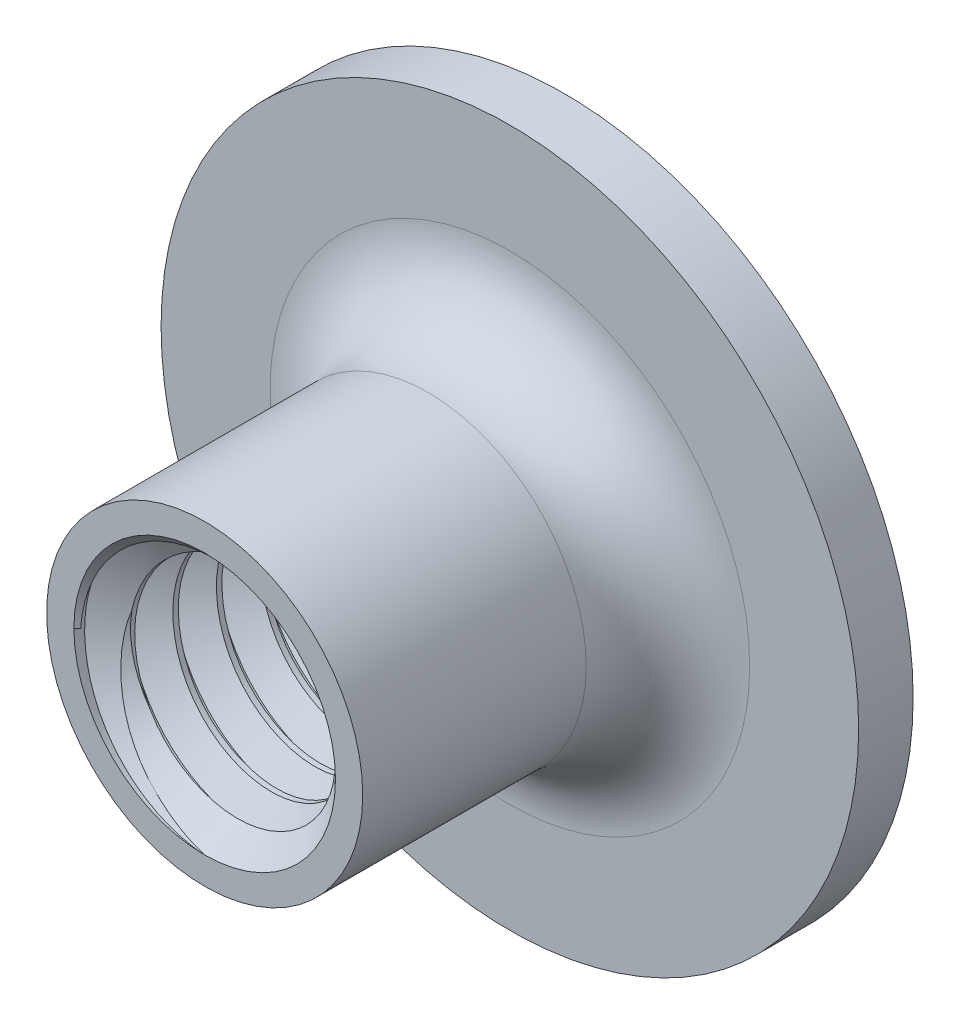
SolidWorks part; units mm, degrees
ref_plane "Front Plane" through (0, 0, 0) normal (0, 0, 1) x (1, 0, 0)
ref_plane "Top Plane" through (0, 0, 0) normal (0, 1, 0) x (1, 0, 0)
ref_plane "Right Plane" through (0, 0, 0) normal (1, 0, 0) x (0, 0, -1)
sketch "Sketch1" plane through (0, 0, 0) normal (0, 0, 1) x (1, 0, 0)
  circle A0 centre (0, 0) radius 12.7
  circle A1 centre (0, 0) radius 4.7625
  dimension "D1" = 9.525
extrude "Extrude1" add sketch "Sketch1" along normal blind 1.9844
sketch "Sketch2" plane through (0, 0, 1.9844) normal (0, 0, 1) x (1, 0, 0)
  circle A0 centre (0, 0) radius 5.7547
  circle A1 centre (0, 0) radius 4.7625
extrude "Extrude2" add sketch "Sketch2" along normal blind 11.1125
sketch "Sketch3" plane through (0, 0, 0) normal (0, 0, -1) x (-1, 0, 0)
  circle A0 centre (0, 0) radius 4.7625 construction
  circle A1 centre (0, 0) radius 4.7625
curve "Helix/Spiral1" pitch 1.5875 height 14.2875 turns 9 parameters "pitch"=1.5875
sketch "Sketch4" plane through (0, 0, 0) normal (0, 1, 0) x (1, 0, 0)
  line L0 (-4.7625, 1.3891) -> (-4.7625, 0)
  line L1 (-4.7625, 0) -> (-3.7314, 0.5953)
  line L2 (-3.7314, 0.5953) -> (-3.7314, 0.7938)
  line L3 (-3.7314, 0.7938) -> (-4.7625, 1.3891)
  line L4 (-3.7314, 0.6945) -> (-4.7625, 0.6945) construction
  line L5 (-4.2469, 0.2977) -> (-4.2469, 1.0914) construction
  dimension "D1" = 0.1984
  dimension "D2" = 0.7937
  dimension "D3" = 60
sweep "Sweep1" add profiles "Sketch4" path "Helix/Spiral1"
sketch "Sketch5" plane through (0, 0, 0) normal (0, 0, -1) x (-1, 0, 0)
  circle A1 centre (0, 0) radius 12.7
  circle A2 centre (0, 0) radius 12.7
  dimension "D1" = 0
extrude "Cut-Extrude1" cut sketch "Sketch5" along normal through all
sketch "Sketch6" plane through (0, 0, 0) normal (0, 0, -1) x (-1, 0, 0)
  circle A0 centre (0, 0) radius 4.7625 construction
  circle A1 centre (0, 0) radius 4.7625
extrude "Cut-Extrude2" cut sketch "Sketch6" against normal through all draft 45
sketch "Sketch7" plane through (0, 0, 13.0969) normal (0, 0, 1) x (1, 0, 0)
  circle A1 centre (0, 0) radius 5.7547
  circle A2 centre (0, 0) radius 5.7547
  dimension "D1" = 0
extrude "Cut-Extrude3" cut sketch "Sketch7" along normal through all
sketch "Sketch8" plane through (0, 0, 13.0969) normal (0, 0, 1) x (1, 0, 0)
  circle A0 centre (0, 0) radius 4.7625 construction
  circle A1 centre (0, 0) radius 4.7625
extrude "Cut-Extrude4" cut sketch "Sketch8" against normal through all draft 45
fillet "Fillet1" radius 2.9766 1 edges at (5.7547, 0, 1.9844)
equation "\"D1@Sketch1\" = \"OD@Sketch2\""
equation "\"D3@Helix/Spiral1\" = \"height@Extrude2\"+.125"
equation "\"D1@Sketch4\" = \"pitch@Helix/Spiral1\"*.125"
equation "\"D2@Sketch4\" = \"pitch@Helix/Spiral1\"*.5"
equation "\"D1@Fillet1\" = \"base thickness@Extrude1\"*1.50"
